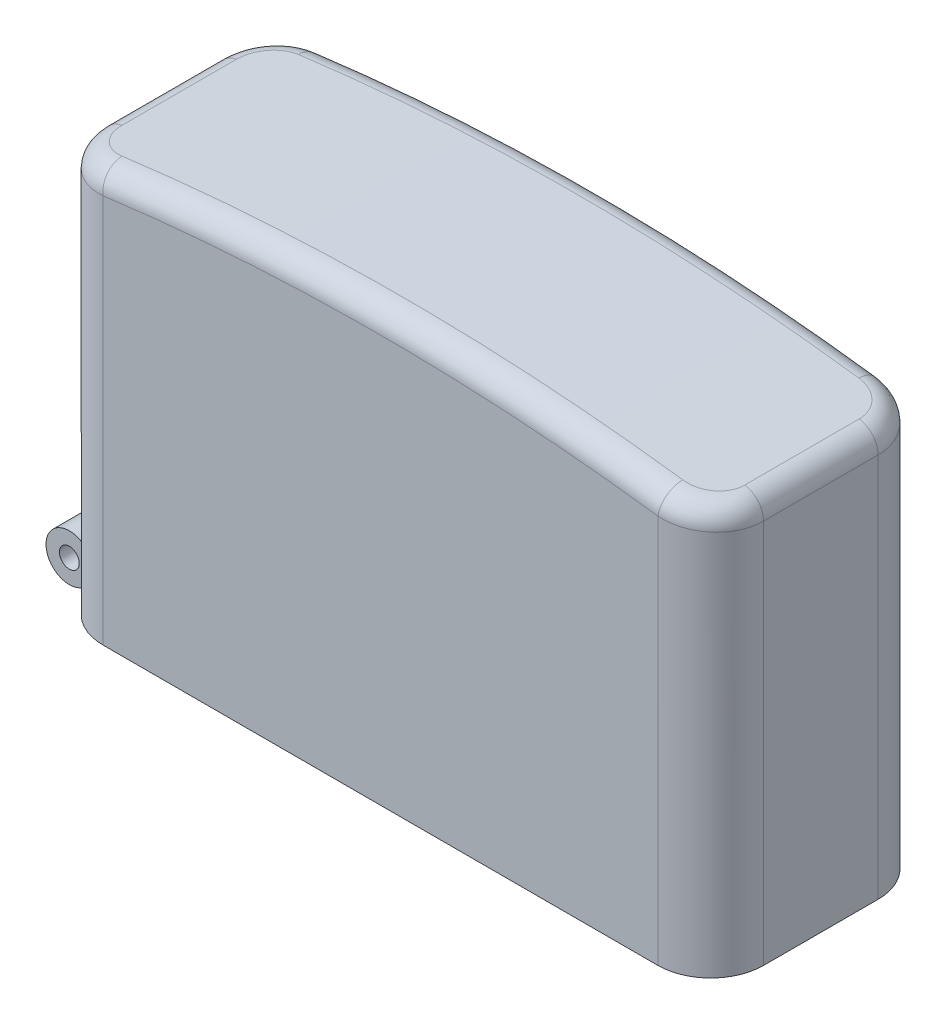
SolidWorks part; units mm, degrees
material "Chrome Stainless Steel"
ref_plane "Front Plane" through (0, 0, 0) normal (0, 0, 1) x (1, 0, 0)
ref_plane "Top Plane" through (0, 0, 0) normal (0, 1, 0) x (1, 0, 0)
ref_plane "Right Plane" through (0, 0, 0) normal (1, 0, 0) x (0, 0, -1)
sketch "Sketch1" plane through (0, 0, 0) normal (0, 0, 1) x (1, 0, 0)
  line L3 (0, 0) -> (38.1, 0)
  line L7 (0, 0) -> (0, 23.2918)
  line L8 (38.1, 0) -> (38.1, 23.2918)
  line L9 (19.05, 0) -> (19.05, 24.7583) construction
  arc A9 (0, 23.2918) -> (38.1, 23.2918) centre (19.05, -99.7017) cw
  point P2 (19.05, 22.8533)
  dimension "D1" = 124.46
  dimension "D3" = 23.2918
  dimension "D7" = 38.1
extrude "Boss-Extrude1" add sketch "Sketch1" along normal blind 12.7
fillet "Fillet7" radius 3.048 4 edges at (38.1, 11.6459, 0) (38.1, 11.6459, 12.7) (0, 11.6459, 0) (0, 11.6459, 12.7)
fillet "Fillet8" radius 1.27 8 edges at (0, 23.2918, 6.35) (1.1304, 23.4616, 0.6788) (19.05, 24.7583, 0) (37.4449, 23.3915, 1.1601) (38.1, 23.2918, 6.35) (36.9696, 23.4616, 12.0212) (19.05, 24.7583, 12.7) (0.6551, 23.3915, 11.5399)
shell "Shell2" thickness 0.4572 removed face at (19.05, 0, 6.35)
sketch "Sketch2" plane through (0, 0, 0) normal (-1, 0, 0) x (0, 0, 1)
  line L0 (10.3251, 0) -> (2.3749, 0)
  line L5 (6.35, 22.1985) -> (6.35, 0) construction
  line L6 (9.652, 22.1985) -> (3.048, 22.1985) construction
  line L11 (0, 0) -> (3.048, 0) construction
  line L12 (2.3749, 0) -> (2.3749, 1.016)
  line L13 (2.3749, 1.016) -> (10.3251, 1.016)
  line L14 (10.3251, 0) -> (10.3251, 1.016)
  point P11 (6.35, 1.016)
  dimension "D1" = 7.9502
  dimension "D2" = 1.016
extrude "Cut-Extrude1" cut sketch "Sketch2" against normal blind 11.7856
sketch "Sketch4" plane through (0, 1.016, 0) normal (0, -1, 0) x (1, 0, 0)
  line L0 (0.0753, 7.1501) -> (-1.2709, 7.1501)
  line L1 (0.0753, 10.3251) -> (-1.2709, 10.3251)
  line L3 (0.0753, 8.7376) -> (-1.2709, 8.7376)
  line L5 (0.0753, 5.5626) -> (-1.2709, 5.5626)
  line L6 (-1.2709, 7.1501) -> (-1.2709, 5.5626)
  line L7 (0.0753, 3.9751) -> (-1.2709, 3.9751)
  line L8 (0.0753, 7.1501) -> (0.0753, 5.5626)
  line L9 (0.0753, 2.3876) -> (-1.2709, 2.3876)
  line L10 (-1.2709, 3.9751) -> (-1.2709, 2.3876)
  line L11 (0.0753, 3.9751) -> (0.0753, 2.3876)
  line L13 (-1.2709, 10.3251) -> (-1.2709, 8.7376)
  line L14 (0.0753, 10.3251) -> (0.0753, 8.7376)
  line L15 (-1.2709, 10.3251) -> (-1.2709, 2.3876) construction
  line L16 (-0.7014, 2.3876) -> (-0.7014, 12.6095) construction
  dimension "D1" = 1.5875
  dimension "D2" = 1.3462
revolve "Revolve1" add sketch "Sketch4" angle 360 about L15
sketch "Sketch5" plane through (0, 0, 2.3876) normal (0, 0, -1) x (-1, 0, 0)
  circle A0 centre (1.2709, 1.016) radius 0.5715
  arc A1 (-0.0753, 1.016) -> (-0.0724, 1.1035) centre (1.2709, 1.016) ccw construction
  dimension "D1" = 1.143
extrude "Cut-Extrude2" cut sketch "Sketch5" against normal through all
